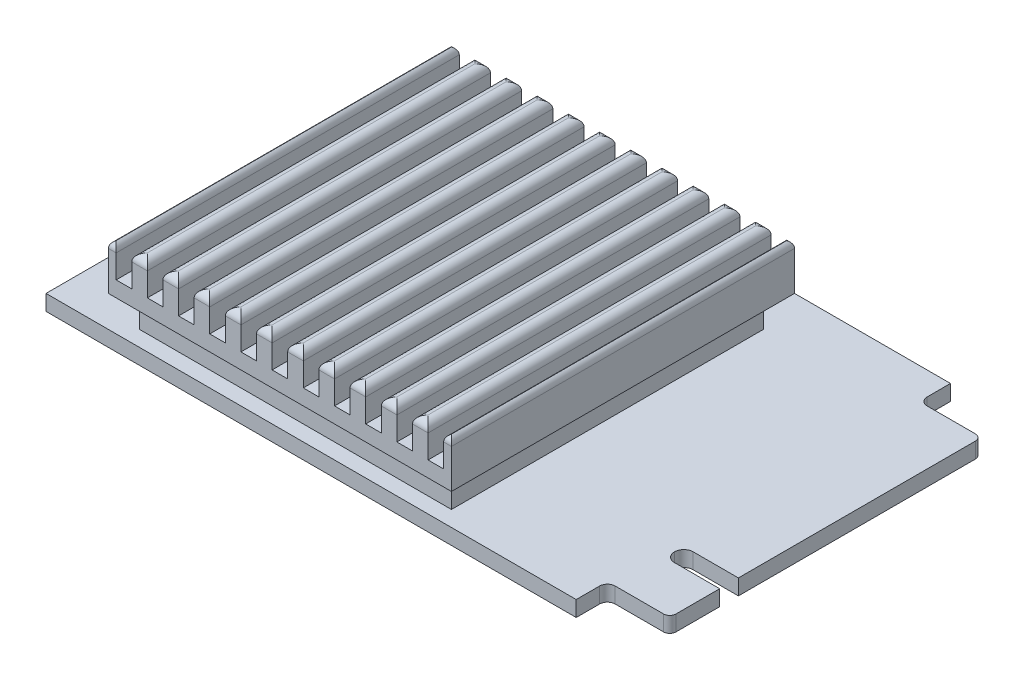
SolidWorks part; units mm, degrees
ref_plane "Front" through (0, 0, 0) normal (0, 0, 1) x (1, 0, 0)
ref_plane "Top" through (0, 0, 0) normal (0, 1, 0) x (1, 0, 0)
ref_plane "Right" through (0, 0, 0) normal (1, 0, 0) x (0, 0, -1)
sketch "草图1" plane through (0, 0, 0) normal (0, 1, 0) x (1, 0, 0)
  line L1 (17, -12) -> (-17, -12)
  line L2 (17, -12) -> (17, 12)
  line L3 (17, 12) -> (-17, 12)
  line L4 (-17, -12) -> (-17, 12)
  line L5 (17, -12) -> (-17, 12) construction
  line L6 (17, 12) -> (-17, -12) construction
  point P0 (0, 0)
  dimension "D1" = 24
  dimension "D2" = 34
extrude "凸台-拉伸1" add sketch "草图1" along normal blind 1
sketch "草图2" plane through (0, 0, 0) normal (0, 1, 0) x (1, 0, 0)
  line L0 (-7.1428, 0) -> (32.276, 0) construction
  line L1 (21, -10) -> (17, -10)
  line L2 (21, -10) -> (21, 10)
  line L3 (21, 10) -> (17, 10)
  line L4 (17, -10) -> (17, 10)
  line L5 (21, -10) -> (17, 10) construction
  line L6 (21, 10) -> (17, -10) construction
  line L7 (17, -12) -> (17, 12) construction
  point P0 (19, 0)
  dimension "D1" = 20
  dimension "D2" = 4
extrude "凸台-拉伸2" add sketch "草图2" along normal blind 1
sketch "草图3" plane through (0, 1, 0) normal (0, 1, 0) x (1, 0, 0)
  line L0 (21, -10) -> (21, 10) construction
  line L1 (21, -6.8) -> (17.5, -6.8)
  line L2 (21, -6.8) -> (21, -5.6)
  line L3 (21, -5.6) -> (17.5, -5.6)
  line L4 (17.5, -6.8) -> (17.5, -5.6)
  line L5 (21, -6.8) -> (17.5, -5.6) construction
  line L6 (21, -5.6) -> (17.5, -6.8) construction
  line L8 (17, -10) -> (21, -10) construction
  point P0 (19.25, -6.2)
  dimension "D1" = 1.2
  dimension "D2" = 3.5
  dimension "D3" = 3.2
extrude "切除-拉伸1" cut sketch "草图3" against normal through all
fillet "圆角1" radius 0.6 2 edges at (17.5, 0.5, 6.8) (17.5, 0.5, 5.6)
fillet "圆角2" radius 0.5 2 edges at (17, 0.5, -10) (17, 0.5, 10)
fillet "圆角3" radius 0.4 2 edges at (21, 0.5, 10) (21, 0.5, -10)
sketch "草图4" plane through (0, 1, 0) normal (0, 1, 0) x (1, 0, 0)
  line L2 (-17, 12) -> (-17, -12) construction
  line L3 (17, 12) -> (-17, 12) construction
  circle A1 centre (-17, 7) radius 1.5
  dimension "D1" = 3
  dimension "D2" = 5
extrude "切除-拉伸2" cut sketch "草图4" against normal through all
sketch "草图8" plane through (0, 1, 0) normal (0, 1, 0) x (1, 0, 0)
  line L0 (17, 12) -> (-17, 12) construction
  line L1 (8, -11) -> (-12, -11)
  line L2 (8, -11) -> (8, 9)
  line L3 (8, 9) -> (-12, 9)
  line L4 (-12, -11) -> (-12, 9)
  line L5 (8, -11) -> (-12, 9) construction
  line L6 (8, 9) -> (-12, -11) construction
  line L7 (-17, 5.5) -> (-17, -12) construction
  point P0 (-2, -1)
  dimension "D1" = 20
  dimension "D2" = 20
  dimension "D3" = 3
  dimension "D4" = 5
extrude "凸台-拉伸9" add sketch "草图8" along normal blind 2
sketch "草图5" plane through (0, 3, 0) normal (0, 1, 0) x (1, 0, 0)
  line L0 (-17, 12) -> (-17, 8.5) construction
  line L1 (9, -12) -> (-13, -12)
  line L2 (9, -12) -> (9, 10)
  line L3 (9, 10) -> (-13, 10)
  line L4 (-13, -12) -> (-13, 10)
  line L5 (9, -12) -> (-13, 10) construction
  line L6 (9, 10) -> (-13, -12) construction
  line L8 (17, 12) -> (-17, 12) construction
  point P0 (-2, -1)
  dimension "D1" = 22
  dimension "D2" = 22
  dimension "D3" = 4
  dimension "D4" = 2
extrude "凸台-拉伸3" add sketch "草图5" along normal blind 3
sketch "草图6" plane through (0, 6, 0) normal (0, 1, 0) x (1, 0, 0)
  line L0 (-2, 10) -> (-2, -15.0728) construction
  line L1 (9, 10) -> (-13, 10) construction
  line L2 (9, 10) -> (-13, 10) construction
  line L3 (-1.5, -12) -> (-2.5, -12)
  line L4 (-1.5, -12) -> (-1.5, 10)
  line L5 (-1.5, 10) -> (-2.5, 10)
  line L6 (-2.5, -12) -> (-2.5, 10)
  line L7 (-1.5, -12) -> (-2.5, 10) construction
  line L8 (-1.5, 10) -> (-2.5, -12) construction
  line L9 (-13, -12) -> (9, -12) construction
  line L10 (0.5, -12) -> (0.5, 10)
  line L11 (0.5, -12) -> (-0.5, -12)
  line L12 (-0.5, -12) -> (-0.5, 10)
  line L13 (0.5, 10) -> (-0.5, 10)
  line L14 (2.5, -12) -> (2.5, 10)
  line L15 (2.5, -12) -> (1.5, -12)
  line L16 (1.5, -12) -> (1.5, 10)
  line L17 (2.5, 10) -> (1.5, 10)
  line L18 (4.5, -12) -> (4.5, 10)
  line L19 (4.5, -12) -> (3.5, -12)
  line L20 (3.5, -12) -> (3.5, 10)
  line L21 (4.5, 10) -> (3.5, 10)
  line L22 (6.5, -12) -> (6.5, 10)
  line L23 (6.5, -12) -> (5.5, -12)
  line L24 (5.5, -12) -> (5.5, 10)
  line L25 (6.5, 10) -> (5.5, 10)
  line L26 (8.5, -12) -> (8.5, 10)
  line L27 (8.5, -12) -> (7.5, -12)
  line L28 (7.5, -12) -> (7.5, 10)
  line L29 (8.5, 10) -> (7.5, 10)
  line L30 (-3.5, -12) -> (-3.5, 10)
  line L31 (-3.5, -12) -> (-4.5, -12)
  line L32 (-4.5, -12) -> (-4.5, 10)
  line L33 (-3.5, 10) -> (-4.5, 10)
  line L34 (-5.5, -12) -> (-5.5, 10)
  line L35 (-5.5, -12) -> (-6.5, -12)
  line L36 (-6.5, -12) -> (-6.5, 10)
  line L37 (-5.5, 10) -> (-6.5, 10)
  line L38 (-7.5, -12) -> (-7.5, 10)
  line L39 (-7.5, -12) -> (-8.5, -12)
  line L40 (-8.5, -12) -> (-8.5, 10)
  line L41 (-7.5, 10) -> (-8.5, 10)
  line L42 (-9.5, -12) -> (-9.5, 10)
  line L43 (-9.5, -12) -> (-10.5, -12)
  line L44 (-10.5, -12) -> (-10.5, 10)
  line L45 (-9.5, 10) -> (-10.5, 10)
  line L46 (-11.5, -12) -> (-11.5, 10)
  line L47 (-11.5, -12) -> (-12.5, -12)
  line L48 (-12.5, -12) -> (-12.5, 10)
  line L49 (-11.5, 10) -> (-12.5, 10)
  point P4 (-2, -1)
  dimension "D1" = 1
  dimension "D2" = 6
  dimension "D3" = 6
extrude "切除-拉伸3" cut sketch "草图6" against normal blind 2
sketch "草图7" plane through (0, 6, 0) normal (0, 1, 0) x (1, 0, 0)
  line L1 (8.0317, -9.8487) -> (-11.9683, -9.8487)
  line L2 (8.0317, -9.8487) -> (8.0317, 10.1513)
  line L3 (8.0317, 10.1513) -> (-11.9683, 10.1513)
  line L4 (-11.9683, -9.8487) -> (-11.9683, 10.1513)
  line L5 (8.0317, -9.8487) -> (-11.9683, 10.1513) construction
  line L6 (8.0317, 10.1513) -> (-11.9683, -9.8487) construction
  point P0 (-1.9683, 0.1513)
  point P7 (0, 0)
  dimension "D1" = 20
  dimension "D2" = 20
extrude "凸台-拉伸8" [suppressed] add sketch "草图7" along normal blind 4
fillet "圆角4" radius 0.5 48 edges at (8.75, 6, -10) (9, 6, 1) (8.75, 6, 12) (8.5, 6, 1) (7, 6, -10) (7.5, 6, 1) (7, 6, 12) (6.5, 6, 1) (5, 6, -10) (5.5, 6, 1) (5, 6, 12) (4.5, 6, 1) (3, 6, -10) (3.5, 6, 1) (3, 6, 12) (2.5, 6, 1) (1, 6, -10) (1.5, 6, 1) (1, 6, 12) (0.5, 6, 1) (-1, 6, 12) (-1.5, 6, 1) (-1, 6, -10) (-0.5, 6, 1) (-3, 6, -10) (-2.5, 6, 1) (-3, 6, 12) (-3.5, 6, 1) (-5, 6, 12) (-5.5, 6, 1) (-5, 6, -10) (-4.5, 6, 1) (-7, 6, 12) (-7.5, 6, 1) (-7, 6, -10) (-6.5, 6, 1) (-9, 6, -10) (-8.5, 6, 1) (-9, 6, 12) (-9.5, 6, 1) (-11, 6, -10) (-10.5, 6, 1) (-11, 6, 12) (-11.5, 6, 1) (-12.75, 6, 12) (-13, 6, 1) (-12.75, 6, -10) (-12.5, 6, 1)
